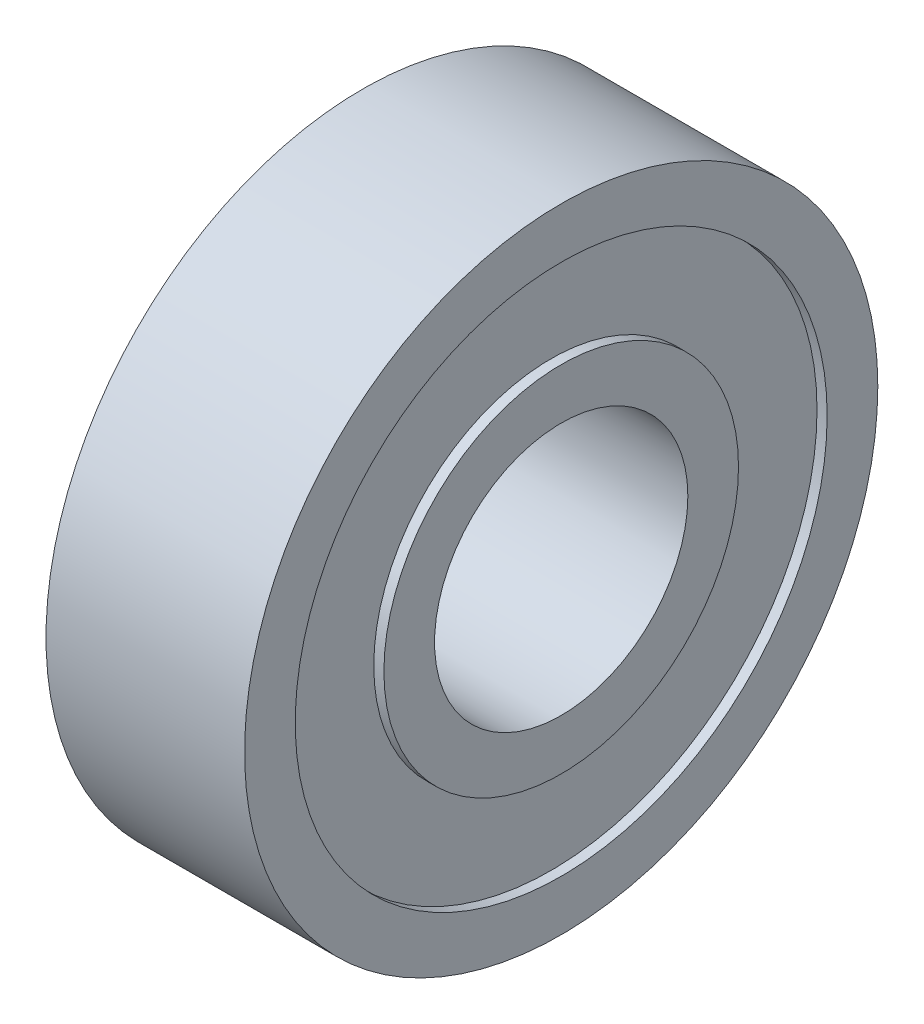
SolidWorks part; units mm, degrees
material "AISI 304"
ref_plane "Front Plane" through (0, 0, 0) normal (0, 0, 1) x (1, 0, 0)
ref_plane "Top Plane" through (0, 0, 0) normal (0, 1, 0) x (1, 0, 0)
ref_plane "Right Plane" through (0, 0, 0) normal (1, 0, 0) x (0, 0, -1)
sketch "Sketch1" plane through (0, 0, 0) normal (1, 0, 0) x (0, 0, -1)
  circle A0 centre (0, 0) radius 3.175
  circle A1 centre (0, 0) radius 7.9375
  dimension "D1" = 6.35
  dimension "D2" = 15.875
extrude "Boss-Extrude1" add sketch "Sketch1" along normal mid plane 4.9784
sketch "Sketch2" plane through (2.4892, 0, 0) normal (1, 0, 0) x (0, 0, -1)
  circle A0 centre (0, 0) radius 4.445
  circle A1 centre (0, 0) radius 6.6675
  circle A2 centre (0, 0) radius 7.9375 construction
  circle A3 centre (0, 0) radius 3.175 construction
  dimension "D1" = 1.27
  dimension "D2" = 1.27
extrude "Cut-Extrude1" cut sketch "Sketch2" against normal blind 0.254
mirror "Mirror1" about plane through (0, 0, 0) normal (1, 0, 0) of "Cut-Extrude1"
